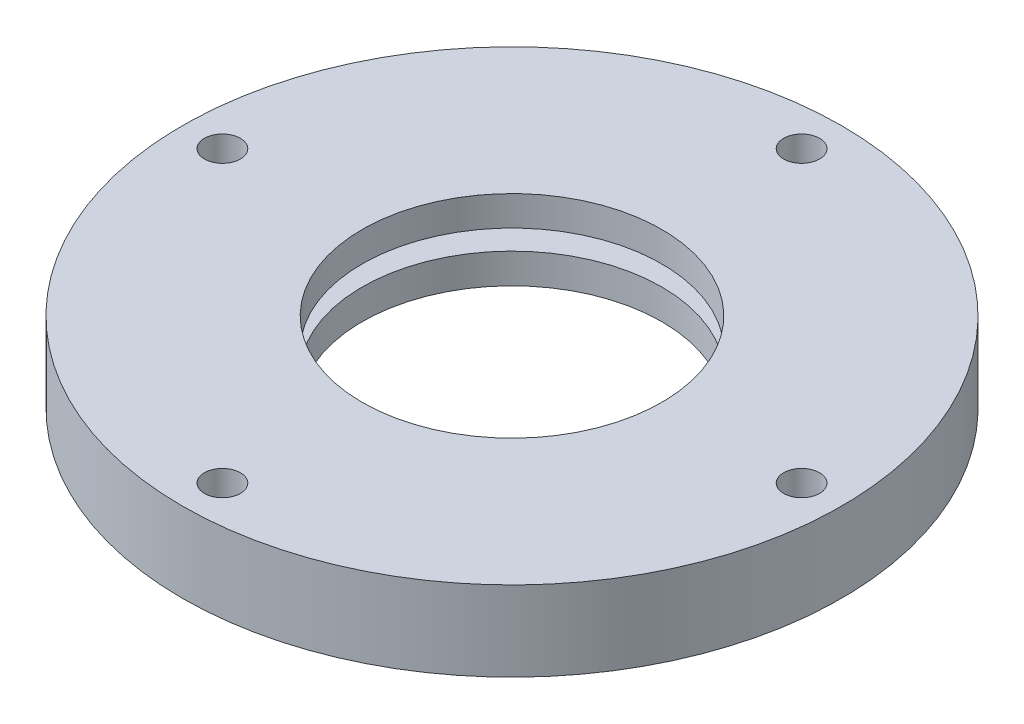
SolidWorks part; units mm, degrees
ref_plane "Front Plane" through (0, 0, 0) normal (0, 0, 1) x (1, 0, 0)
ref_plane "Top Plane" through (0, 0, 0) normal (0, 1, 0) x (1, 0, 0)
ref_plane "Right Plane" through (0, 0, 0) normal (1, 0, 0) x (0, 0, -1)
sketch "Sketch1" plane through (0, 0, 0) normal (0, 1, 0) x (1, 0, 0)
  circle A0 centre (0, 0) radius 33
  circle A1 centre (-29, 0) radius 1.5
  circle A2 centre (0, 0) radius 29 construction
  circle A3 centre (0, 29) radius 1.5
  circle A4 centre (29, 0) radius 1.5
  circle A5 centre (0, -29) radius 1.5
  point P15 (0, 0)
  dimension "D1" = 66
  dimension "D2" = 4
  dimension "D3" = 3
  dimension "D4" = 4
extrude "Boss-Extrude1" add sketch "Sketch1" along normal blind 8
hole_wizard "CSK for M3 Flat Head Machine Screw1" positions "Sketch2" profile "Sketch3" countersink size "M3" standard "ANSI Metric" end condition through all
sketch "Sketch2" plane through (0, 0, 0) normal (0, -1, 0) x (-1, 0, 0)
  point P0 (0, -29)
  point P3 (29, 0)
  point P6 (0, 29)
  point P9 (-29, 0)
sketch "Sketch3" plane through (0, 0, 29) normal (1, 0, 0) x (0, 0, -1)
  line L0 (0, 0) -> (0, 8)
  line L1 (0, 8) -> (1.8, 8)
  line L2 (1.8, 8) -> (1.8, 1.35)
  line L3 (1.8, 1.35) -> (3.15, 0)
  line L5 (3.15, 0) -> (0, 0)
  line L6 (-1.8, 1.35) -> (-3.15, 0) construction
  line L11 (0, -6.35) -> (0, 107.95) construction
  dimension "Thru Hole Dia." = 3.6
  dimension "Thru Hole Depth" = 8
  dimension "Near C'Sink Dia." = 6.3
  dimension "Near C'Sink Angle" = 90
sketch "Croquis1" plane through (0, 0, 0) normal (0, -1, 0) x (1, 0, 0)
  circle A0 centre (0, 0) radius 15
  dimension "D1" = 30
extrude "Cortar-Extruir1" cut sketch "Croquis1" against normal up to next
ref_axis "Eje1" through (0, 8, 0) along (0, -1, 0)
ref_plane "Plano1" through (-33, 0, 0) normal (-1, 0, 0) x (0, 0, 1)
sketch "Croquis2" plane through (-33, 0, 0) normal (-1, 0, 0) x (0, 0, 1)
  line L0 (0, 0) -> (0, 8.0219) construction
  line L1 (0, 8) -> (0, 0) construction
  line L3 (-20, 5.0109) -> (20, 5.0109)
  line L4 (-20, 5.0109) -> (-20, 3.0109)
  line L5 (-20, 3.0109) -> (20, 3.0109)
  line L6 (20, 5.0109) -> (20, 3.0109)
  line L7 (-20, 5.0109) -> (20, 3.0109) construction
  line L8 (-20, 3.0109) -> (20, 5.0109) construction
  point P5 (0, 4.0109)
  dimension "D1" = 40
  dimension "D2" = 2
extrude "Cortar-Extruir2" cut sketch "Croquis2" against normal blind 50
